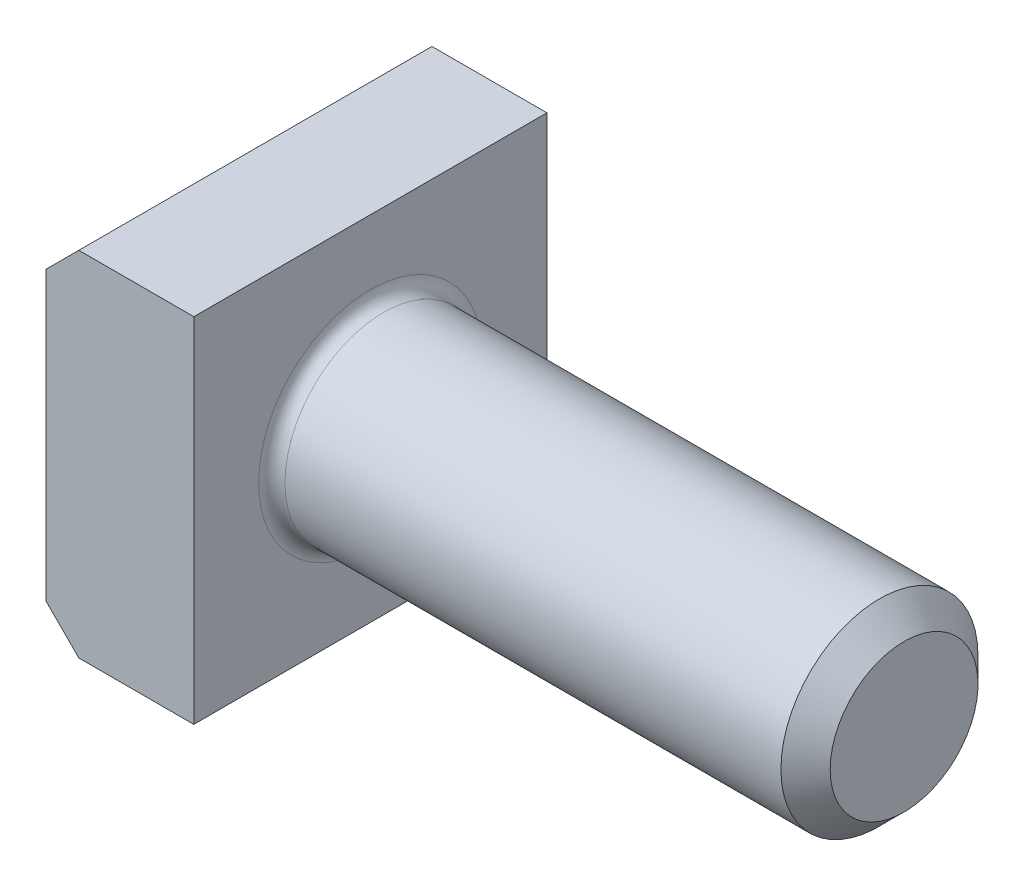
SolidWorks part; units mm, degrees
ref_plane "Front Plane" through (0, 0, 0) normal (0, 0, 1) x (1, 0, 0)
ref_plane "Top Plane" through (0, 0, 0) normal (0, 1, 0) x (1, 0, 0)
ref_plane "Right Plane" through (0, 0, 0) normal (1, 0, 0) x (0, 0, -1)
sketch "BaseBodySke" plane through (0, 0, 0) normal (0, 0, 1) x (1, 0, 0)
  line L0 (-107.4075, 0) -> (214.0904, 0) construction
  line L1 (0, 0) -> (0, 12)
  line L4 (0, 12) -> (65, 12)
  line L5 (65, 12) -> (65, 0)
  line L6 (65, 0) -> (0, 0)
  line L7 (35, 10) -> (35, -17.9005) construction
  line L8 (34.0602, 10.352) -> (57.5082, 10.352) construction
  line L9 (62, 13.8049) -> (62, -14.5195) construction
  dimension "Thread_length" = 30
  dimension "Length" = 65
revolve "BaseBody" add sketch "BaseBodySke" angle 360 about L6
cosmetic thread "ThreadCosmetic" [suppressed] parameters "Thread_length"=30, "Thread_minor"=20.704
sketch "HeadSke" plane through (0, 0, 0) normal (0, 0, 1) x (1, 0, 0)
  line L0 (0, 0) -> (-36.296, 0) construction
  line L1 (-14, 21.5) -> (0, 21.5)
  line L2 (-18, 17.5) -> (-18, -17.5)
  line L3 (-14, -21.5) -> (0, -21.5)
  line L4 (0, 21.5) -> (0, -21.5)
  line L5 (-18, 17.5) -> (-14, 21.5)
  line L6 (-18, -17.5) -> (-14, -21.5)
  point P10 (-18, 0)
  dimension "Head_height" = 18
extrude "Head" add sketch "HeadSke" along normal mid plane 43
sketch "FlatEndSke" plane through (0, 0, 0) normal (0, 0, 1) x (1, 0, 0)
  line L0 (62, 12) -> (65, 12)
  line L1 (65, 12) -> (65, 9)
  line L2 (65, 9) -> (62, 12)
  line L3 (65, -12) -> (65, 12) construction
  line L5 (0, 0) -> (89.7899, 0) construction
  line L7 (65, 12) -> (0, 12) construction
  dimension "D1" = 45
revolve "FlatEnd" cut sketch "FlatEndSke" angle 360 about L5
sketch "CutEndSke" plane through (65, 0, 0) normal (1, 0, 0) x (0, 0, -1)
  circle A0 centre (0, 0) radius 12 construction
  circle A1 centre (0, 0) radius 12
extrude "CutEnd" [suppressed] cut sketch "CutEndSke" against normal blind 3
dome "RoundEnd" [suppressed] faces to dome 1 distance 3 parameters "D1"=3
fillet "Fillet" radius 1.6 1 edges at (0, 0, 12)
sketch "ThdSchSke" plane through (0, 0, 0) normal (0, 0, 1) x (1, 0, 0)
  line L0 (0, 0) -> (89.8666, 0) construction
  line L1 (65, -27.1828) -> (65, 30.5493) construction
  line L2 (59.6, 10.352) -> (58.6485, 12)
  line L3 (58.6485, 12) -> (58.6485, 13.9029)
  line L4 (58.6485, 13.9029) -> (60.5515, 13.9029)
  line L5 (60.5515, 13.9029) -> (60.5515, 12)
  line L6 (60.5515, 12) -> (59.6, 10.352)
  dimension "Length" = 65
  dimension "Advance" = 5.4
  dimension "D1" = 20.704
  dimension "D2" = 24
revolve "ThreadSchematic" [suppressed] cut sketch "ThdSchSke" angle 360 about L0
pattern_linear "ThdSchPat" [suppressed] count 10 spacing 3 along (-1, 0, 0) of bodies 105
equation "\"Thread_minor@ThreadCosmetic\" = \"Minor_dia@BaseBodySke\""
equation "\"Thread_length@ThreadCosmetic\" = \"Thread_length@BaseBodySke\""
equation "\"D1@Head\" = \"Head_width@HeadSke\""
equation "\"D1@CutEnd\" = \"Chamfer_width@FlatEndSke\""
equation "\"D1@RoundEnd\" = \"Chamfer_width@FlatEndSke\""
equation "\"Length@ThdSchSke\" = \"Length@BaseBodySke\""
equation "\"Advance@ThdSchSke\" = \"Advance@BaseBodySke\"*1.8"
equation "\"D2@ThdSchSke\" = \"Diameter@BaseBodySke\""
equation "\"D1@ThdSchSke\" = \"Minor_dia@BaseBodySke\""
equation "\"D3@ThdSchPat\" = \"Advance@BaseBodySke\""
equation "\"D1@ThdSchPat\" =  int( \"Thread_length@BaseBodySke\" / \"Advance@BaseBodySke\" ) "
